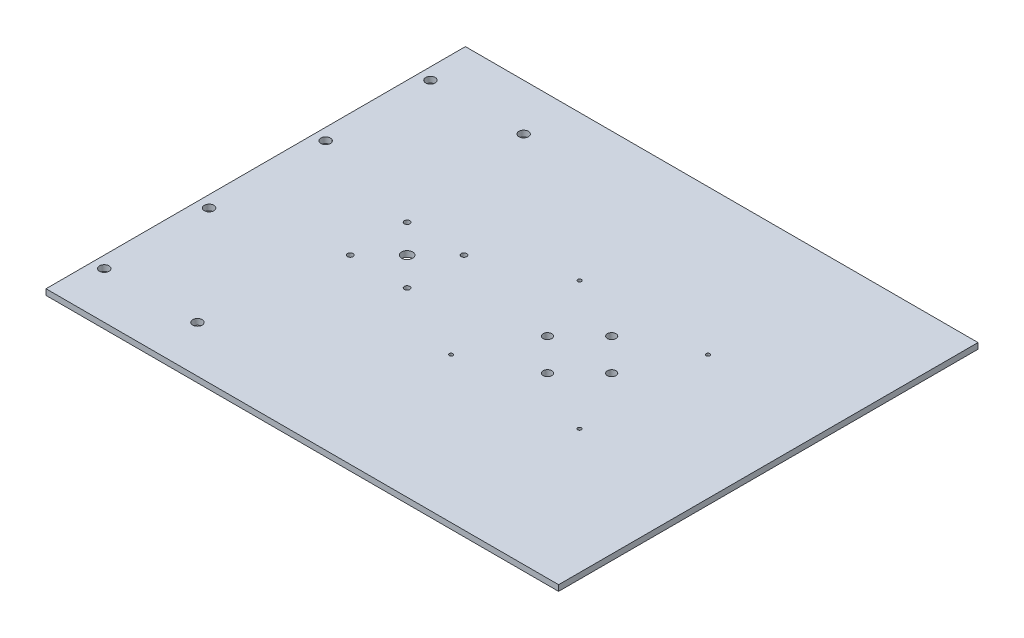
SolidWorks part; units mm, degrees
ref_plane "Front Plane" through (0, 0, 0) normal (0, 0, 1) x (1, 0, 0)
ref_plane "Top Plane" through (0, 0, 0) normal (0, 1, 0) x (1, 0, 0)
ref_plane "Right Plane" through (0, 0, 0) normal (1, 0, 0) x (0, 0, -1)
sketch "Sketch1" plane through (0, 0, 0) normal (0, 1, 0) x (1, 0, 0)
  line L1 (-139.7, -114.3) -> (139.7, -114.3)
  line L2 (-139.7, -114.3) -> (-139.7, 114.3)
  line L3 (-139.7, 114.3) -> (139.7, 114.3)
  line L4 (139.7, -114.3) -> (139.7, 114.3)
  line L5 (-139.7, -114.3) -> (139.7, 114.3) construction
  line L6 (-139.7, 114.3) -> (139.7, -114.3) construction
  point P0 (0, 0)
  dimension "D1" = 228.6
  dimension "D2" = 279.4
extrude "Boss-Extrude1" add sketch "Sketch1" along normal blind 3.175
sketch "Sketch2" plane through (0, 0, 0) normal (0, 1, 0) x (1, 0, 0)
  line L0 (-193.2668, 0) -> (192.9727, 0) construction
sketch "Sketch3" plane through (0, 3.175, 0) normal (0, 1, 0) x (1, 0, 0)
  circle A1 centre (-133.35, -31.75) radius 2.6
  circle A2 centre (-133.35, -31.75) radius 2.6
  circle A3 centre (-82.55, -88.9) radius 2.6
  circle A4 centre (-82.55, -88.9) radius 2.6
  circle A5 centre (-133.35, -88.9) radius 2.6
  circle A6 centre (-133.35, -88.9) radius 2.6
  dimension "D1" = 0
  dimension "D2" = 0
  dimension "D3" = 0
sketch "Sketch5" plane through (0, 3.175, 0) normal (0, 1, 0) x (1, 0, 0)
  circle A0 centre (-41.674, 15.5) radius 1.5 construction
  circle A1 centre (-41.674, -15.5) radius 1.5 construction
  circle A2 centre (-72.674, 15.5) radius 1.5 construction
  circle A3 centre (-72.674, -15.5) radius 1.5 construction
  circle A4 centre (-57.174, 0) radius 2.5 construction
  circle A5 centre (-41.674, 15.5) radius 1.5
  circle A6 centre (-41.674, -15.5) radius 1.5
  circle A7 centre (-72.674, 15.5) radius 1.5
  circle A8 centre (-72.674, -15.5) radius 1.5
  circle A9 centre (-57.174, 0) radius 2.5 construction
  circle A10 centre (-57.174, 0) radius 3.008
  dimension "D1" = 6.016
sketch "Sketch7" plane through (0, 3.175, 0) normal (0, 1, 0) x (1, 0, 0)
  circle A0 centre (71.8318, -35.0018) radius 1 construction
  circle A1 centre (1.8282, -35.0018) radius 1 construction
  circle A2 centre (71.8318, -35.0018) radius 1
  circle A3 centre (1.8282, -35.0018) radius 1
  circle A4 centre (1.8282, 35.0018) radius 1 construction
  circle A5 centre (71.8318, 35.0018) radius 1 construction
  circle A6 centre (1.8282, 35.0018) radius 1
  circle A7 centre (71.8318, 35.0018) radius 1
extrude "Cut-Extrude1" cut sketch "Sketch3" against normal through all
mirror "Mirror1" about plane through (0, 0, 0) normal (0, 0, 1) of "Cut-Extrude1"
extrude "Cut-Extrude2" cut sketch "Sketch5" against normal through all
extrude "Cut-Extrude3" cut sketch "Sketch7" against normal through all
sketch "Sketch8" plane through (0, 3.175, 0) normal (0, 1, 0) x (1, 0, 0)
  arc A0 (36.83, -19.85) -> (36.83, -15.15) centre (36.83, -17.5) ccw construction
  arc A1 (36.83, -19.85) -> (36.83, -15.15) centre (36.83, -17.5) ccw
  arc A2 (36.83, -15.15) -> (36.83, -19.85) centre (36.83, -17.5) ccw construction
  arc A3 (36.83, -15.15) -> (36.83, -19.85) centre (36.83, -17.5) ccw
  circle A4 centre (19.33, 0) radius 2.35 construction
  circle A5 centre (19.33, 0) radius 2.35
  arc A6 (36.83, 15.15) -> (36.83, 19.85) centre (36.83, 17.5) ccw construction
  arc A7 (36.83, 15.15) -> (36.83, 19.85) centre (36.83, 17.5) ccw
  arc A8 (36.83, 19.85) -> (36.83, 15.15) centre (36.83, 17.5) ccw construction
  arc A9 (36.83, 19.85) -> (36.83, 15.15) centre (36.83, 17.5) ccw
  circle A10 centre (54.33, 0) radius 2.35 construction
  circle A11 centre (54.33, 0) radius 2.35
extrude "Cut-Extrude4" cut sketch "Sketch8" against normal through all
equation "\"tightTol\"= 0.005in"
equation "\"normTol\"= 0.01in"
equation "\"looseTol\"= 0.02in"
equation "\"D1@Sketch5\"=5mm+2*\"looseTol\""
